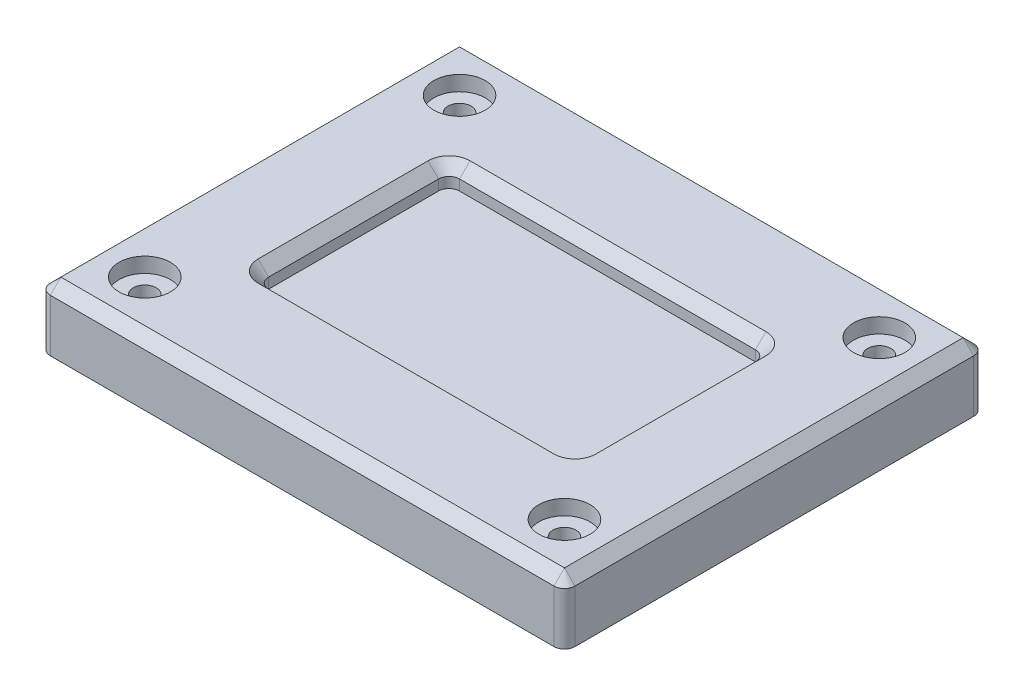
SolidWorks part; units mm, degrees
ref_plane "Front Plane" through (0, 0, 0) normal (0, 0, 1) x (1, 0, 0)
ref_plane "Top Plane" through (0, 0, 0) normal (0, 1, 0) x (1, 0, 0)
ref_plane "Right Plane" through (0, 0, 0) normal (1, 0, 0) x (0, 0, -1)
sketch "Sketch1" plane through (0, 0, 0) normal (0, 1, 0) x (1, 0, 0)
  line L1 (-62.5, -50) -> (62.5, -50)
  line L2 (-62.5, -50) -> (-62.5, 50)
  line L3 (-62.5, 50) -> (62.5, 50)
  line L4 (62.5, -50) -> (62.5, 50)
  line L5 (-62.5, -50) -> (62.5, 50) construction
  line L6 (-62.5, 50) -> (62.5, -50) construction
  point P0 (0, 0)
  dimension "D1" = 125
  dimension "D2" = 100
extrude "Boss-Extrude1" add sketch "Sketch1" along normal blind 15
sketch "Sketch2" plane through (0, 15, 0) normal (0, 1, 0) x (1, 0, 0)
  line L1 (-37.75, -22.75) -> (37.75, -22.75)
  line L2 (-37.75, -22.75) -> (-37.75, 22.75)
  line L3 (-37.75, 22.75) -> (37.75, 22.75)
  line L4 (37.75, -22.75) -> (37.75, 22.75)
  line L5 (-37.75, -22.75) -> (37.75, 22.75) construction
  line L6 (-37.75, 22.75) -> (37.75, -22.75) construction
  point P0 (0, 0)
  dimension "D1" = 75.5
  dimension "D2" = 45.5
extrude "Cut-Extrude1" cut sketch "Sketch2" against normal blind 5
fillet "Fillet1" radius 2.5 4 edges at (-37.75, 12.5, 22.75) (37.75, 12.5, 22.75) (37.75, 12.5, -22.75) (-37.75, 12.5, -22.75)
chamfer "Chamfer2" distance 2.5 angle 45 8 edges at (0, 15, 22.75) (37.0178, 15, 22.0178) (-37.0178, 15, 22.0178) (37.75, 15, 0) (-37.75, 15, 0) (37.0178, 15, -22.0178) (-37.0178, 15, -22.0178) (0, 15, -22.75)
hole_wizard "CBORE for M5 Hex Head Bolt1" positions "Sketch3" profile "Sketch4" counterbore size "M5" standard "ANSI Metric" end condition through all
sketch "Sketch3" plane through (0, 15, 0) normal (0, 1, 0) x (1, 0, 0)
  line L0 (62.5, 50) -> (-62.5, 50) construction
  line L1 (62.5, -50) -> (62.5, 50) construction
  point P0 (50, 37.5)
  dimension "D1" = 12.5
  dimension "D2" = 12.5
sketch "Sketch4" plane through (50, 15, -37.5) normal (1, 0, 0) x (0, 0, 1)
  line L0 (0, 0) -> (0, 15)
  line L1 (0, 15) -> (2.75, 15)
  line L3 (2.75, 15) -> (2.75, 3.58)
  line L4 (2.75, 3.58) -> (6.12, 3.58)
  line L5 (6.12, 3.58) -> (6.12, 0)
  line L7 (6.12, 0) -> (0, 0)
  line L11 (0, -6.35) -> (0, 107.95) construction
  dimension "Thru Hole Dia." = 5.5
  dimension "Thru Hole Depth" = 15
  dimension "C'Bore Dia." = 12.24
  dimension "C'Bore Depth" = 3.58
pattern_linear "LPattern2" count 2 spacing 75 along (0, 0, 1) count 2 spacing 100 along (-1, 0, 0) of "CBORE for M5 Hex Head Bolt1"
fillet "Fillet2" radius 2.5 4 edges at (-62.5, 7.5, -50) (62.5, 7.5, -50) (62.5, 7.5, 50) (-62.5, 7.5, 50)
chamfer "Chamfer3" distance 2.5 angle 45 8 edges at (62.5, 15, 0) (61.7678, 15, -49.2678) (61.7678, 15, 49.2678) (0, 15, -50) (0, 15, 50) (-61.7678, 15, -49.2678) (-61.7678, 15, 49.2678) (-62.5, 15, 0)
